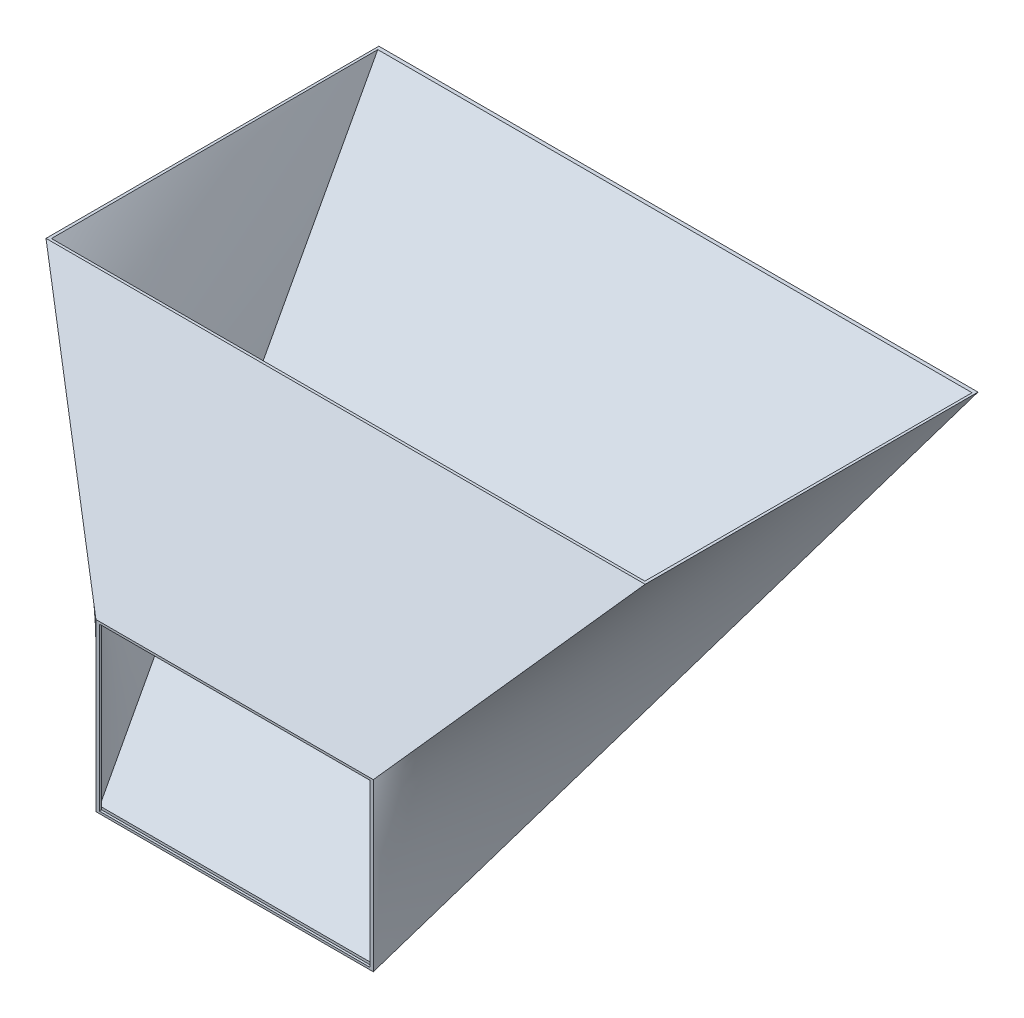
SolidWorks part; units mm, degrees
ref_plane "Front Plane" through (0, 0, 0) normal (0, 0, 1) x (1, 0, 0)
ref_plane "Top Plane" through (0, 0, 0) normal (0, 1, 0) x (1, 0, 0)
ref_plane "Right Plane" through (0, 0, 0) normal (1, 0, 0) x (0, 0, -1)
sketch "Sketch1" plane through (0, 0, 0) normal (0, 1, 0) x (1, 0, 0)
  line L1 (-270, -150) -> (270, -150)
  line L2 (-270, -150) -> (-270, 150)
  line L3 (-270, 150) -> (270, 150)
  line L4 (270, -150) -> (270, 150)
  line L5 (-270, -150) -> (270, 150) construction
  line L6 (-270, 150) -> (270, -150) construction
  point P0 (0, 0)
  dimension "D1" = 300
  dimension "D2" = 540
ref_plane "Plane1" through (0, 0, 250) normal (0, 0, 1) x (1, 0, 0)
sketch "Sketch2" plane through (0, 0, 0) normal (1, 0, 0) x (0, 0, -1)
  line L0 (0, 0) -> (-250, -250)
  line L1 (-250, 297) -> (-250, -297) construction
  line L2 (-150, 0) -> (150, 0) construction
  dimension "D1" = 45
  dimension "D2" = 250
sketch "Sketch3" plane through (0, 0, 250) normal (0, 0, 1) x (1, 0, 0)
  line L0 (0, 0) -> (0, -250) construction
  line L1 (-125, -325) -> (125, -325)
  line L2 (-125, -325) -> (-125, -175)
  line L3 (-125, -175) -> (125, -175)
  line L4 (125, -325) -> (125, -175)
  line L5 (-125, -325) -> (125, -175) construction
  line L6 (-125, -175) -> (125, -325) construction
  line L7 (0, -137.5) -> (0, 137.5) construction
  point P0 (0, -250)
  dimension "D1" = 250
  dimension "D2" = 150
  dimension "D3" = 250
loft "Loft1" add profiles "Sketch1", "Sketch3" connector at (270, 0, 150) connector at (125, -175, 250)
shell "Shell1" thickness 2 removed face at (0, 0, 0)
sketch "Sketch4" plane through (0, 0, 250) normal (0, 0, 1) x (1, 0, 0)
  line L0 (125, -175) -> (-125, -175) construction
  line L1 (-122, -323) -> (122, -323)
  line L2 (-122, -323) -> (-122, -177)
  line L3 (-122, -177) -> (122, -177)
  line L4 (122, -323) -> (122, -177)
  line L5 (-122, -323) -> (122, -177) construction
  line L6 (-122, -177) -> (122, -323) construction
  point P0 (0, -250)
  dimension "D1" = 2
  dimension "D2" = 244
extrude "Cut-Extrude1" cut sketch "Sketch4" against normal blind 2
